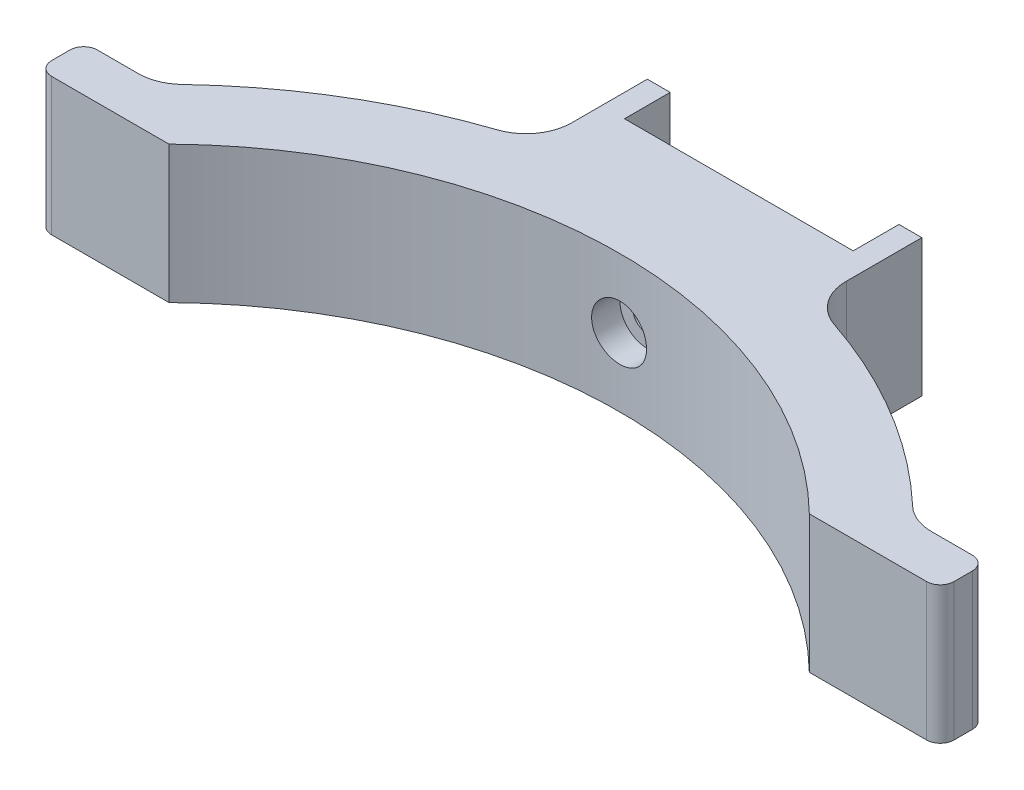
SolidWorks part; units mm, degrees
ref_plane "Front Plane" through (0, 0, 0) normal (0, 0, 1) x (1, 0, 0)
ref_plane "Top Plane" through (0, 0, 0) normal (0, 1, 0) x (1, 0, 0)
ref_plane "Right Plane" through (0, 0, 0) normal (1, 0, 0) x (0, 0, -1)
sketch "Sketch1" plane through (0, 0, 0) normal (0, 1, 0) x (1, 0, 0)
  line L0 (-70, 0) -> (0, 0) construction
  line L1 (-76.315, 5) -> (-84.315, 5)
  line L2 (-84.315, 5) -> (-84.315, 0)
  line L3 (-84.315, 0) -> (-70, 0)
  line L4 (-35, 22.2929) -> (-35, -35.7071) construction
  line L5 (14.315, 5) -> (14.315, 0)
  line L6 (6.315, 5) -> (14.315, 5)
  line L7 (14.315, 0) -> (0, 0)
  line L8 (-50, 32.2929) -> (-20, 32.2929)
  line L9 (-20, 32.2929) -> (-20, 20.3196)
  line L10 (-50, 32.2929) -> (-50, 20.3196)
  line L11 (-35, 22.2929) -> (-35, 32.2929) construction
  arc A0 (0, 0) -> (-70, 0) centre (-35, -35.7071) ccw
  arc A1 (-76.315, 5) -> (6.315, 5) centre (-35, -35.7071) cw
  dimension "D2" = 50
  dimension "D3" = 8
  dimension "D1" = 70
  dimension "D4" = 5
  dimension "D5" = 8
  dimension "D6" = 30
  dimension "D7" = 10
extrude "Boss-Extrude1" add sketch "Sketch1" along normal blind 15 contours A1 L1 L2 L3 A0 L7 L5 L6 | L10 A1 L9 L8 region at (-63.672, 0, -13.5436) region at (-35, 0, -26.9501)
fillet "Fillet1" radius 5 4 edges at (6.315, 7.5, -5) (-76.315, 7.5, -5) (-50, 7.5, -20.3196) (-20, 7.5, -20.3196)
fillet "Fillet2" radius 1.5 4 edges at (-84.315, 7.5, 0) (-84.315, 7.5, -5) (14.315, 7.5, 0) (14.315, 7.5, -5)
sketch "Sketch2" plane through (0, 15, 0) normal (0, 1, 0) x (1, 0, 0)
  line L0 (-50, 32.2929) -> (-20, 32.2929) construction
  line L1 (-47.5, 32.2929) -> (-22.5, 32.2929)
  line L2 (-47.5, 32.2929) -> (-47.5, 27.2929)
  line L3 (-47.5, 27.2929) -> (-22.5, 27.2929)
  line L4 (-22.5, 32.2929) -> (-22.5, 27.2929)
  line L5 (-35, 14.2929) -> (-35, 32.2929) construction
  arc A0 (0, 0) -> (-70, 0) centre (-35, -35.7071) ccw construction
  dimension "D1" = 25
  dimension "D2" = 5
extrude "Cut-Extrude1" cut sketch "Sketch2" against normal through all
sketch "Sketch3" plane through (0, 0, -27.2929) normal (0, 0, -1) x (-1, 0, 0)
  line L0 (22.5, 15) -> (47.5, 0) construction
  circle A0 centre (35, 7.5) radius 1.6
  dimension "D1" = 3.2
extrude "Cut-Extrude2" cut sketch "Sketch3" against normal through all
ref_axis "Axis1" through (-35, 7.5, -14.177) along (0, 0, -1)
ref_plane "Plane2" through (0, 0, 0) normal (0, 0, 1) x (1, 0, 0)
sketch "Sketch4" plane through (0, 0, 0) normal (0, 0, 1) x (1, 0, 0)
  circle A0 centre (-35, 7.5) radius 3
  dimension "D1" = 6
extrude "Cut-Extrude3" cut sketch "Sketch4" against normal offset from surface (17.2929 mm away) 10 up to face at (-36.6, 7.5, -27.2929)
